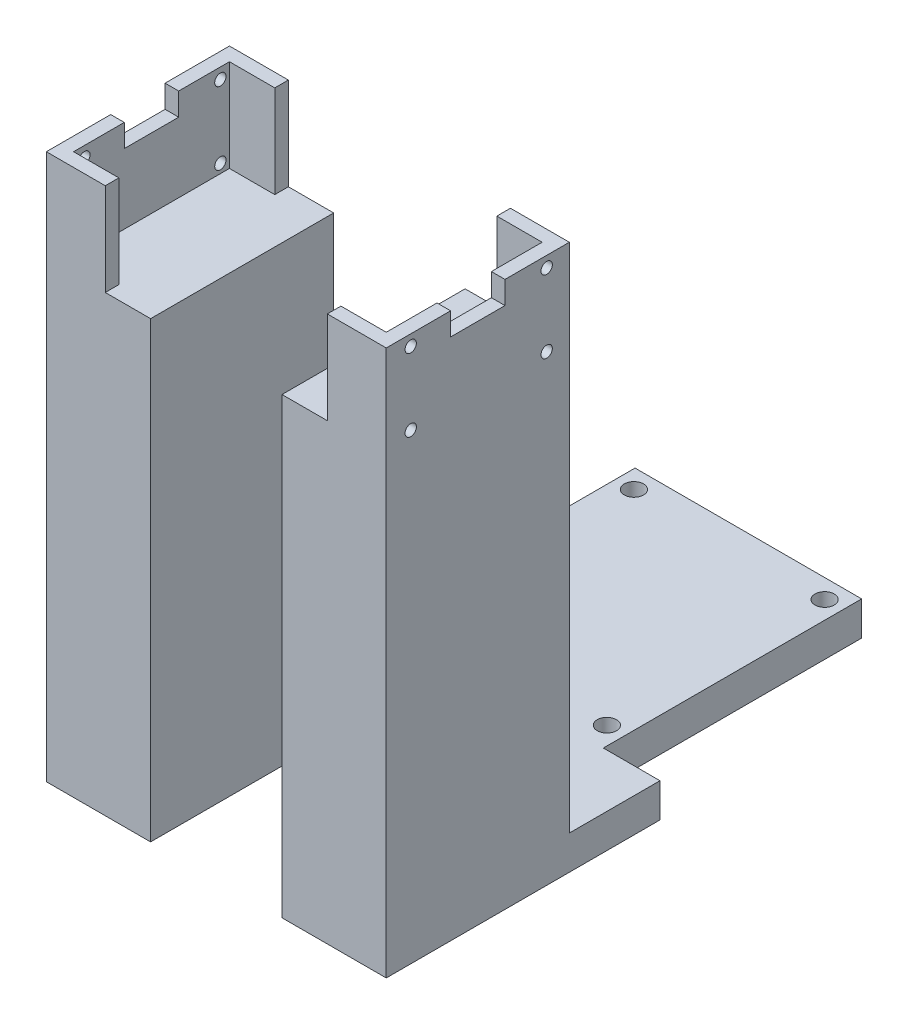
SolidWorks part; units mm, degrees
ref_plane "Front Plane" through (0, 0, 0) normal (0, 0, 1) x (1, 0, 0)
ref_plane "Top Plane" through (0, 0, 0) normal (0, 1, 0) x (1, 0, 0)
ref_plane "Right Plane" through (0, 0, 0) normal (1, 0, 0) x (0, 0, -1)
sketch "Sketch1" plane through (0, 0, 0) normal (0, 1, 0) x (1, 0, 0)
  line L0 (0, 110.0784) -> (0, -110.0784) construction
  line L1 (94.5305, 0) -> (-94.5305, 0) construction
  line L2 (-14.5, -17.2) -> (-14.5, 17.2)
  line L3 (-14.5, 17.2) -> (-34.5, 17.2)
  line L4 (-34.5, 17.2) -> (-34.5, -17.2)
  line L5 (-14.5, -17.2) -> (-34.5, -17.2)
  line L6 (14.5, -17.2) -> (34.5, -17.2)
  line L7 (34.5, 17.2) -> (34.5, -17.2)
  line L8 (14.5, 17.2) -> (34.5, 17.2)
  line L9 (14.5, -17.2) -> (14.5, 17.2)
  line L10 (-34.5, 17.2) -> (-37.5, 17.2)
  line L11 (-24.5, 17.2) -> (-24.5, 20.2)
  line L12 (-24.5, 20.2) -> (-37.5, 20.2)
  line L13 (-37.5, 20.2) -> (-37.5, -20.2)
  line L14 (-37.5, -20.2) -> (-24.5, -20.2)
  line L15 (-24.5, -20.2) -> (-24.5, -17.2)
  line L16 (-34.5, -17.2) -> (-37.5, -17.2)
  line L17 (-24.5, 20.2) -> (-14.5, 20.2)
  line L18 (-14.5, 20.2) -> (-14.5, -20.2)
  line L19 (-24.5, -20.2) -> (-14.5, -20.2)
  point P4 (0, 0)
  point P8 (0, 0)
  point P11 (-14.5, 0)
  point P14 (-34.5, 0)
  point P15 (-14.5, 0)
  point P19 (14.5, 0)
  point P20 (34.5, 0)
  dimension "D1" = 20
  dimension "D2" = 17.2
  dimension "D3" = 14.5
  dimension "D4" = 3
  dimension "D5" = 3
  dimension "D6" = 40.4
sketch "Sketch2" plane through (0, 0, 0) normal (1, 0, 0) x (0, 0, -1)
  line L0 (-17.2, 0) -> (-17.2, 20.4)
  line L1 (17.2, 0) -> (-17.2, 0) construction
  line L2 (-17.2, 20.4) -> (17.2, 20.4)
  line L3 (17.2, 20.4) -> (17.2, 0)
  line L4 (17.2, 0) -> (-17.2, 0)
  line L5 (-17.2, 10.2) -> (17.2, 10.2) construction
  line L6 (0, 0) -> (0, 20.4) construction
  circle A0 centre (-14.8, 18) radius 1.25
  circle A2 centre (-14.8, 2) radius 1.25
  circle A3 centre (15.2, 2) radius 1.25
  circle A4 centre (15.2, 18) radius 1.25
  point P17 (0, 0)
  point P18 (0, 0)
  dimension "D2" = 2.5
  dimension "D3" = 7.8
  dimension "D7" = 15.2
  dimension "D8" = 15.2
  dimension "D1" = 20.4
  dimension "D4" = 14.8
  dimension "D5" = 8.2
  dimension "D6" = 14.8
extrude "Boss-Extrude1" add sketch "Sketch2" against normal blind 3 from offset 34.5 offset against normal yes
extrude "Boss-Extrude2" add sketch "Sketch1" along normal up to surface (20.4 mm away) contours L14 L15 L5 L4 L10 L13 | L12 L13 L10 L3 L11 region at (-31, 0, 18.7) region at (-31, 0, -18.7) up to face at (-36, 20.4, 0)
extrude "Boss-Extrude3" add sketch "Sketch1<3>" against normal blind 3 contours L5 L2 L3 L4 | L15 L19 L18 L5 | L5 L16 L13 L14 L15 | L16 L4 L10 L13 | L12 L13 L10 L3 L11 | L18 L17 L11 L3 region at (-24.5, 0, 0) region at (-19.5, 0, 18.7) region at (-19.5, 0, -18.7) region at (-31, 0, 18.7) region at (-31, 0, -18.7) region at (-36, 0, 0)
sketch "Sketch1<3>" plane through (0, 0, 0) normal (0, 1, 0) x (1, 0, 0) same geometry as "Sketch1"
extrude "Boss-Extrude4" add sketch "Sketch1<4>" against normal blind 100 contours L16 L4 L10 L13 | L5 L16 L13 L14 L15 | L15 L19 L18 L5 | L5 L2 L3 L4 | L12 L13 L10 L3 L11 | L18 L17 L11 L3 region at (-24.5, 0, 0) region at (-19.5, 0, 18.7) region at (-19.5, 0, -18.7) region at (-31, 0, 18.7) region at (-31, 0, -18.7) region at (-36, 0, 0)
sketch "Sketch1<4>" plane through (0, 0, 0) normal (0, 1, 0) x (1, 0, 0) same geometry as "Sketch1"
sketch "Sketch4" plane through (-34.5, 0, 0) normal (1, 0, 0) x (0, 0, -1)
  line L0 (17.2, 20.4) -> (-17.2, 20.4) construction
  line L1 (-6, 25.4) -> (6, 25.4)
  line L2 (-6, 25.4) -> (-6, 15.4)
  line L3 (-6, 15.4) -> (6, 15.4)
  line L4 (6, 25.4) -> (6, 15.4)
  line L5 (0, 15.4) -> (0, 25.4) construction
  line L6 (-6, 20.4) -> (6, 20.4) construction
  point P0 (0, 20.4)
  dimension "D1" = 10
  dimension "D2" = 12
extrude "Cut-Extrude1" cut sketch "Sketch4" against normal blind 132
mirror "Mirror6" about plane through (0, 0, 0) normal (1, 0, 0) of bodies 107
sketch "Sketch7" plane through (0, -100, 0) normal (0, -1, 0) x (1, 0, 0)
  line L0 (-14.5, -20.2) -> (14.5, -20.2)
  line L1 (37.5, -20.2) -> (37.5, -40.2)
  line L2 (37.5, -40.2) -> (-37.5, -40.2)
  line L3 (-37.5, -40.2) -> (-37.5, -20.2)
  line L4 (14.5, -20.2) -> (37.5, -20.2) construction
  line L5 (-14.5, -20.2) -> (-37.5, -20.2) construction
  line L6 (14.5, -20.2) -> (37.5, -20.2)
  line L7 (-14.5, -20.2) -> (-37.5, -20.2)
  line L8 (15, -32.5) -> (15, -28.5) construction
  line L9 (21, -32.5) -> (21, -28.5) construction
  line L10 (-21, -32.5) -> (-21, -28.5) construction
  line L11 (-15, -32.5) -> (-15, -28.5) construction
  line L12 (15, -32.5) -> (15, -28.5)
  line L13 (21, -32.5) -> (21, -28.5)
  line L14 (-21, -32.5) -> (-21, -28.5)
  line L15 (-15, -32.5) -> (-15, -28.5)
  line L16 (-21.035, -44.95) -> (-21.035, -92.99) construction
  line L17 (-25, -40.2) -> (25, -40.2)
  line L18 (-25, -40.2) -> (-25, -97.2)
  line L19 (-25, -97.2) -> (25, -97.2)
  line L20 (25, -40.2) -> (25, -97.2)
  line L21 (-21.035, -92.99) -> (21.035, -92.99) construction
  arc A0 (15, -32.5) -> (21, -32.5) centre (18, -32.5) ccw construction
  arc A1 (21, -28.5) -> (15, -28.5) centre (18, -28.5) ccw construction
  arc A2 (-21, -32.5) -> (-15, -32.5) centre (-18, -32.5) ccw construction
  arc A3 (-15, -28.5) -> (-21, -28.5) centre (-18, -28.5) ccw construction
  arc A4 (15, -32.5) -> (21, -32.5) centre (18, -32.5) ccw
  arc A5 (21, -28.5) -> (15, -28.5) centre (18, -28.5) ccw
  arc A6 (-21, -32.5) -> (-15, -32.5) centre (-18, -32.5) ccw
  arc A7 (-15, -28.5) -> (-21, -28.5) centre (-18, -28.5) ccw
  circle A8 centre (-21.035, -44.95) radius 2.125
  circle A9 centre (-21.035, -92.99) radius 2.125
  circle A10 centre (21.035, -92.99) radius 2.125
  circle A11 centre (21.035, -44.95) radius 2.125
  point P23 (0, -97.2)
  point P36 (0, -92.99)
  line M4 (14.5, -20.2) -> (37.5, -20.2)
  dimension "D4" = 4.25
  dimension "D5" = 4.25
  dimension "D8" = 4.25
  dimension "D9" = 4.25
  dimension "D1" = 20
  dimension "D2" = 57
  dimension "D3" = 50
  dimension "D6" = 48.04
  dimension "D7" = 42.07
  dimension "D10" = 48.04
  dimension "D11" = 42.07
  dimension "D12" = 4.21
extrude "Boss-Extrude5" add sketch "Sketch7" against normal blind 7.5 contours L0 L7 L3 L2 L1 A7 L15 A6 L14 A5 L13 A4 L12 M4 | L20 L2 L18 L19 A11 A10 A9 A8 region at (0, -100, -30.1775) region at (0, -100, -68.6945)
sketch "Sketch8" plane through (0, 0, 0) normal (0, 1, 0) x (1, 0, 0)
  line L0 (-47.2197, 74.2041) -> (9.7803, 74.2041)
  line L3 (-47.2197, 74.2041) -> (-47.2197, 26.2041)
  line L4 (-47.2197, 26.2041) -> (9.7803, 26.2041)
  line L5 (9.7803, 74.2041) -> (9.7803, 26.2041)
  circle A0 centre (7.2259, 71.2552) radius 2.125
  circle A1 centre (-40.8141, 71.2552) radius 2.125
  circle A2 centre (-40.8141, 29.1852) radius 2.125
  circle A3 centre (7.2259, 29.1852) radius 2.125
  point P0 (0, 0)
  point P2 (0, 0)
  point P29 (19.4172, 66.1692)
  dimension "D3" = 4.25
  dimension "D1" = 48.04
  dimension "D2" = 42.07
sketch "Sketch9" plane through (0, 0, 0) normal (0, 0, 1) x (1, 0, 0)
  line L0 (37.5, -26.283) -> (42.3357, -13.6761) construction
  line L1 (37.5, 20.4) -> (37.5, -100) construction
  line L2 (42.3357, -13.6761) -> (37.5, -13.6761) construction
  line L3 (37.5, -13.6761) -> (42.3357, -13.6761)
  line L4 (42.3357, -13.6761) -> (37.5, -26.283)
  line L5 (37.5, -26.283) -> (37.5, -13.6761)
